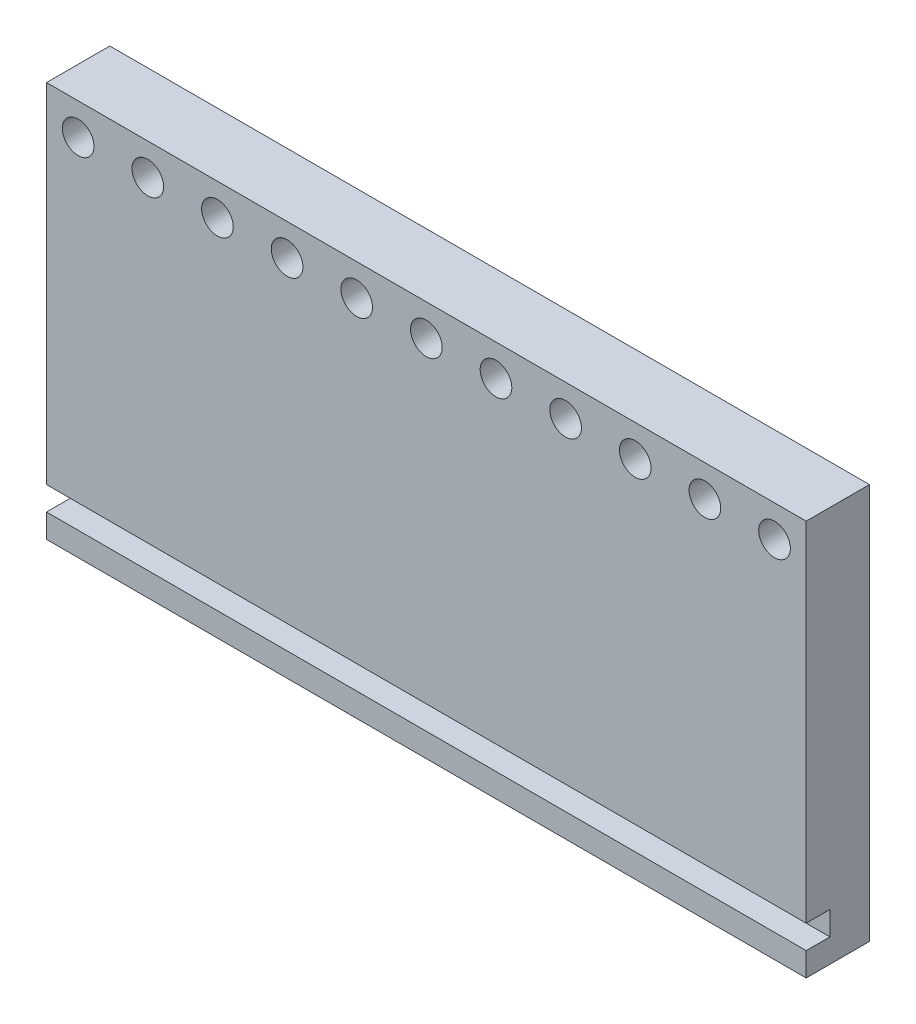
SolidWorks part; units mm, degrees
ref_plane "Front" through (0, 0, 0) normal (0, 0, 1) x (1, 0, 0)
ref_plane "Top" through (0, 0, 0) normal (0, 1, 0) x (1, 0, 0)
ref_plane "Right" through (0, 0, 0) normal (1, 0, 0) x (0, 0, -1)
sketch "Sketch1" plane through (0, 0, 0) normal (0, 1, 0) x (1, 0, 0)
  line L1 (-152.4, -12.7) -> (152.4, -12.7)
  line L2 (-152.4, -12.7) -> (-152.4, 12.7)
  line L3 (-152.4, 12.7) -> (152.4, 12.7)
  line L4 (152.4, -12.7) -> (152.4, 12.7)
  line L5 (-152.4, -12.7) -> (152.4, 12.7) construction
  line L6 (-152.4, 12.7) -> (152.4, -12.7) construction
  point P0 (0, 0)
  dimension "D1" = 304.8
  dimension "D2" = 25.4
extrude "Boss-Extrude1" add sketch "Sketch1" along normal mid plane 158.75 contours L3 L4 L1 L2
sketch "Sketch2" plane through (-152.4, 0, 0) normal (-1, 0, 0) x (0, 0, 1)
  line L0 (12.7, 79.375) -> (12.7, -79.375) construction
  line L1 (3.175, -60.325) -> (12.7, -60.325)
  line L2 (3.175, -60.325) -> (3.175, -69.85)
  line L3 (3.175, -69.85) -> (12.7, -69.85)
  line L4 (12.7, -60.325) -> (12.7, -69.85)
  line L5 (3.175, -60.325) -> (12.7, -69.85) construction
  line L6 (3.175, -69.85) -> (12.7, -60.325) construction
  line L7 (12.7, -79.375) -> (-12.7, -79.375) construction
  point P0 (7.9375, -65.0875)
  dimension "D1" = 9.525
  dimension "D2" = 9.525
  dimension "D3" = 19.05
extrude "Cut-Extrude1" cut sketch "Sketch2" against normal up to next
sketch "Sketch3" plane through (0, 0, 12.7) normal (0, 0, 1) x (1, 0, 0)
  line L0 (152.4, 79.375) -> (152.4, -60.325) construction
  line L1 (-152.4, 79.375) -> (152.4, 79.375) construction
  point P0 (139.7, 66.675)
  dimension "D1" = 12.7
  dimension "D2" = 12.7
hole_wizard "1/2 (0.5000) Dowel Hole1" positions "Sketch4" profile "Sketch6" hole size "1/2" standard "ANSI Inch"
sketch "Sketch4" plane through (0, 0, 12.7) normal (0, 0, 1) x (1, 0, 0)
  point P0 (139.7, 66.675)
sketch "Sketch6" plane through (139.7, 66.675, 12.7) normal (1, 0, 0) x (0, -1, 0)
  line L0 (0, 0) -> (0, 20.3255)
  line L1 (0, 20.3255) -> (6.35, 16.51)
  line L2 (6.35, 16.51) -> (6.35, 0)
  line L5 (6.35, 0) -> (0, 0)
  line L10 (0, 20.3255) -> (-6.35, 16.51) construction
  line L11 (0, -6.35) -> (0, 107.95) construction
  dimension "Hole Dia." = 12.7
  dimension "Hole Depth" = 16.51
  dimension "Drill Angle" = 118
pattern_linear "LPattern1" count 11 spacing 27.94 along (-1, 0, 0) of "1/2 (0.5000) Dowel Hole1"
